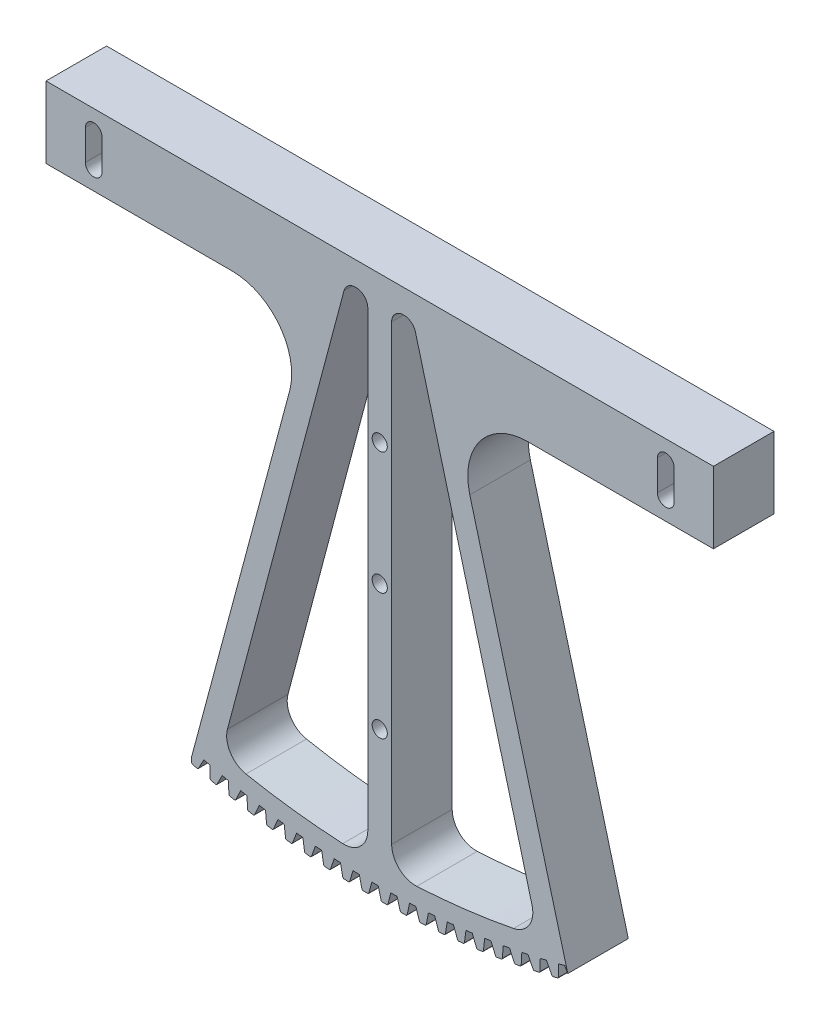
SolidWorks part; units mm, degrees
ref_plane "Front Plane" through (0, 0, 0) normal (0, 0, 1) x (1, 0, 0)
ref_plane "Top Plane" through (0, 0, 0) normal (0, 1, 0) x (1, 0, 0)
ref_plane "Right Plane" through (0, 0, 0) normal (1, 0, 0) x (0, 0, -1)
sketch "Sketch3" plane through (0, 0, 0) normal (0, 0, 1) x (1, 0, 0)
  line L0 (0, 0) -> (0, -304.8) construction
  line L1 (-21.234, -79.2464) -> (-78.888, -294.4142)
  line L2 (21.234, -79.2464) -> (78.888, -294.4142)
  line L4 (-140, -79.56) -> (140, -79.56)
  line L5 (-140, -79.56) -> (-140, -109.56)
  line L6 (-140, -109.56) -> (140, -109.56)
  line L7 (140, -79.56) -> (140, -109.56)
  line L8 (0, -109.56) -> (0, -79.56) construction
  line L9 (-140, -94.56) -> (140, -94.56) construction
  arc A0 (-78.888, -294.4142) -> (78.888, -294.4142) centre (0, 0) ccw
  point P269 (0, -94.56)
  dimension "D1" = 304.8
  dimension "D4" = 79.56
  dimension "D5" = 30
  dimension "D6" = 280
  dimension "D7" = 140
extrude "Boss-Extrude2" add sketch "Sketch3" along normal blind 25.4 contours L7 L4 L2 L6 | L1 L6 L2 L4 | L1 L4 L2 | L5 L6 L1 L4 | L1 A0 L2 L6 region at (0, -95.3531, 0) region at (-82.6452, -94.3847, 0) region at (0, -220.3694, 0) region at (82.6452, -94.3847, 0)
fillet "Fillet1" radius 25 2 edges at (-29.3565, -109.56, 12.7) (29.3565, -109.56, 12.7)
sketch "Sketch4" plane through (0, -79.56, 0) normal (0, 1, 0) x (1, 0, 0)
  line L1 (-140, 0) -> (140, 0)
  line L2 (-140, 0) -> (-140, -25.4)
  line L3 (-140, -25.4) -> (140, -25.4)
  line L4 (140, 0) -> (140, -25.4)
  line L5 (0, -25.4) -> (0, 0) construction
  line L6 (-140, -12.7) -> (140, -12.7) construction
  point P252 (0, -12.7)
sketch "Sketch5" plane through (0, 0, 0) normal (0, 0, -1) x (-1, 0, 0)
  line L0 (-123.5, -94.56) -> (-123.5, -100.91)
  line L1 (-116.5, -94.56) -> (-116.5, -100.91)
  line L2 (116.5, -94.56) -> (116.5, -88.21)
  line L3 (140, -79.56) -> (-140, -79.56) construction
  line L4 (-120, -88.21) -> (-120, -100.91) construction
  line L5 (0, -79.56) -> (0, -109.56) construction
  line L6 (-116.5, -94.56) -> (-116.5, -88.21)
  line L7 (-123.5, -94.56) -> (-123.5, -88.21)
  line L8 (116.5, -94.56) -> (116.5, -100.91)
  line L9 (123.5, -94.56) -> (123.5, -100.91)
  line L10 (123.5, -94.56) -> (123.5, -88.21)
  line L11 (-140, -79.56) -> (-140, -109.56) construction
  line L12 (120, -88.21) -> (120, -100.91) construction
  arc A1 (-116.5, -88.21) -> (-123.5, -88.21) centre (-120, -88.21) ccw
  arc A2 (-123.5, -100.91) -> (-116.5, -100.91) centre (-120, -100.91) ccw
  arc A3 (123.5, -100.91) -> (116.5, -100.91) centre (120, -100.91) cw
  arc A4 (116.5, -88.21) -> (123.5, -88.21) centre (120, -88.21) cw
  dimension "D1" = 16.5
  dimension "D2" = 7
  dimension "D3" = 8.65
  dimension "D5" = 3.5
  dimension "D4" = 6.35
sketch "Sketch13" plane through (0, 0, 0) normal (0, 0, -1) x (-1, 0, 0)
  line L0 (0, 0) -> (78.888, -294.4142)
  line L1 (0, 0) -> (-78.888, -294.4142)
  arc A0 (-78.888, -294.4142) -> (78.888, -294.4142) centre (0, 0) ccw
  arc A1 (-78.888, -294.4142) -> (78.888, -294.4142) centre (0, 0) ccw construction
  arc A2 (-78.888, -294.4142) -> (78.888, -294.4142) centre (0, 0) ccw
  circle A3 centre (0, 0) radius 304.8
  dimension "D1" = 609.6
sketch "Sketch14" plane through (0, 0, 0) normal (0, 0, -1) x (-1, 0, 0)
  line L0 (0, 0) -> (80.0203, -298.6399) construction
  line L2 (78.888, -294.4142) -> (78.9109, -297.0369)
  line L3 (78.9109, -297.0369) -> (76.2891, -297.7211)
  line L18 (76.2891, -297.7211) -> (75.0275, -295.4216)
  line L20 (0, 0) -> (-79.2746, -295.8555) construction
  line L32 (78.888, -294.4142) -> (75.0275, -295.4216)
  line L33 (75.0275, -295.4216) -> (78.888, -294.4142)
  line L34 (0, 0) -> (-75.3952, -296.8678) construction
  line L35 (0, 0) -> (-71.5028, -297.8293) construction
  line L36 (0, 0) -> (-67.5982, -298.7397) construction
  line L37 (0, 0) -> (-63.6821, -299.5989) construction
  line L38 (0, 0) -> (-59.755, -300.4068) construction
  line L39 (0, 0) -> (-55.8176, -301.1633) construction
  line L40 (0, 0) -> (-51.8707, -301.8681) construction
  line L41 (0, 0) -> (-47.9149, -302.5212) construction
  line L42 (0, 0) -> (-43.951, -303.1225) construction
  line L43 (0, 0) -> (-39.9794, -303.6718) construction
  line L44 (0, 0) -> (-36.0011, -304.1691) construction
  line L45 (0, 0) -> (-32.0165, -304.6143) construction
  line L46 (0, 0) -> (-28.0265, -305.0073) construction
  line L47 (0, 0) -> (-24.0316, -305.348) construction
  line L48 (0, 0) -> (-20.0327, -305.6364) construction
  line L49 (0, 0) -> (-16.0303, -305.8724) construction
  line L50 (0, 0) -> (-12.0252, -306.0561) construction
  line L51 (0, 0) -> (-8.018, -306.1873) construction
  line L52 (0, 0) -> (-4.0094, -306.266) construction
  line L53 (0, 0) -> (-0.0002, -306.2922) construction
  line L54 (0, 0) -> (4.0091, -306.266) construction
  line L55 (0, 0) -> (8.0176, -306.1873) construction
  line L56 (0, 0) -> (12.0248, -306.0561) construction
  line L57 (0, 0) -> (16.03, -305.8725) construction
  line L58 (0, 0) -> (20.0323, -305.6364) construction
  line L59 (0, 0) -> (24.0313, -305.348) construction
  line L60 (0, 0) -> (28.0261, -305.0073) construction
  line L61 (0, 0) -> (32.0162, -304.6143) construction
  line L62 (0, 0) -> (36.0007, -304.1691) construction
  line L63 (0, 0) -> (39.9791, -303.6719) construction
  line L64 (0, 0) -> (43.9506, -303.1225) construction
  line L65 (0, 0) -> (47.9146, -302.5213) construction
  line L66 (0, 0) -> (51.8704, -301.8682) construction
  line L67 (0, 0) -> (55.8173, -301.1633) construction
  line L68 (0, 0) -> (59.7546, -300.4069) construction
  line L69 (0, 0) -> (63.6817, -299.599) construction
  line L70 (0, 0) -> (67.5979, -298.7398) construction
  line L71 (0, 0) -> (71.5025, -297.8293) construction
  line L72 (0, 0) -> (75.3948, -296.8679) construction
  line L73 (0, 0) -> (-79.2746, -295.8555) construction
  line L74 (0, 0) -> (-75.3952, -296.8678) construction
  line L137 (37.789, -141.0305) -> (78.888, -294.4142) construction
  line L138 (-140, -79.56) -> (-140, -109.56)
  line L139 (-140, -109.56) -> (-61.9371, -109.56)
  line L140 (-37.789, -141.0305) -> (-78.888, -294.4142)
  line L141 (78.888, -294.4142) -> (37.789, -141.0305)
  line L142 (61.9371, -109.56) -> (140, -109.56)
  line L143 (140, -109.56) -> (140, -79.56)
  line L144 (140, -79.56) -> (-140, -79.56)
  line L145 (-140, -79.56) -> (-140, -109.56)
  line L146 (-140, -109.56) -> (-61.9371, -109.56)
  line L147 (-37.789, -141.0305) -> (-78.888, -294.4142)
  line L149 (61.9371, -109.56) -> (140, -109.56)
  line L150 (140, -109.56) -> (140, -79.56)
  line L151 (140, -79.56) -> (-140, -79.56)
  circle A0 centre (0, 0) radius 307.34
  circle A1 centre (0, 0) radius 302.26
  arc A3 (-37.789, -141.0305) -> (-61.9371, -109.56) centre (-61.9371, -134.56) ccw
  arc A5 (61.9371, -109.56) -> (37.789, -141.0305) centre (61.9371, -134.56) ccw
  arc A6 (-37.789, -141.0305) -> (-61.9371, -109.56) centre (-61.9371, -134.56) ccw
  arc A8 (61.9371, -109.56) -> (37.789, -141.0305) centre (61.9371, -134.56) ccw
  arc A11 (-78.888, -294.4142) -> (78.888, -294.4142) centre (0, 0) ccw
  arc A12 (-78.888, -294.4142) -> (78.888, -294.4142) centre (0, 0) ccw
  arc M181 (-78.888, -294.4142) -> (78.888, -294.4142) centre (0, 0) ccw
  dimension "D5" = 614.68
  dimension "D6" = 30
  dimension "D7" = 40
  dimension "D4" = 604.52
  dimension "D1" = 14.5
  dimension "D3" = 14.5
  dimension "D8" = 0.75
  dimension "D9" = 306.2922
  dimension "D10" = 0.75
  dimension "D2" = 0
extrude "Boss-Extrude4" add sketch "Sketch14" against normal up to surface (25.4 mm away) contours L2 M181 region at (-77.2591, -296.0724, 0) up to face at (0, -146.6727, 25.4)
sketch "Sketch15" plane through (0, 0, 0) normal (1, 0, 0) x (0, 0, -1)
  line L0 (0, 0) -> (-23.3364, 0) construction
sketch "Sketch16" plane through (0, 0, 0) normal (0, 0, -1) x (-1, 0, 0)
  line L0 (75.0275, -295.4216) -> (73.7653, -293.1208)
  line L1 (73.7653, -293.1208) -> (71.1999, -293.7544)
  line L2 (71.1999, -293.7544) -> (71.1541, -296.3784)
  line L3 (0, 0) -> (71.5025, -297.8293) construction
  line L4 (0, 0) -> (75.3948, -296.8679) construction
  circle A0 centre (0, 0) radius 302.26 construction
  arc A1 (-78.888, -294.4142) -> (78.888, -294.4142) centre (0, 0) ccw construction
  dimension "D1" = 14.5
  dimension "D2" = 14.5
extrude "Cut-Extrude2" cut sketch "Sketch16" against normal through all and the other way through all
fillet "Fillet4" radius 0.5 2 edges at (-76.2891, -297.7211, 12.7) (-78.9109, -297.0369, 12.7)
pattern_circular "CirPattern8" count 20 every 1.5 about axis through (0, 0, 0) along (0, 0, 1) of "Cut-Extrude2", "Boss-Extrude4", "Fillet4"
extrude "Cut-Extrude3" cut sketch "Sketch5" against normal through all
sketch "Sketch17" plane through (0, 0, 25.4) normal (0, 0, 1) x (1, 0, 0)
  line L0 (0, -89.56) -> (0, -140.87) construction
  line L1 (-4.9975, -89.56) -> (-13.9975, -89.56) construction
  line L2 (5, -89.56) -> (13.9975, -89.56) construction
  line L3 (0, 0) -> (78.888, -294.4142) construction
  line L4 (13.9975, -89.56) -> (5, -89.56) construction
  line L5 (0, 0) -> (-78.888, -294.4142) construction
  line L6 (5, -192.18) -> (41.3123, -192.18) construction
  line L7 (-13.9975, -89.56) -> (-11.3363, -79.56) construction
  line L8 (-13.9975, -89.56) -> (-69.1613, -296.8497) construction
  line L9 (-74.9529, -279.7282) -> (-65.2893, -282.2998) construction
  line L10 (-4.9975, -192.1745) -> (-41.3052, -192.1745) construction
  line L11 (13.9975, -89.56) -> (69.1728, -296.8504) construction
  line L12 (64.3749, -278.8253) -> (73.8713, -275.6914) construction
  line L13 (-140, -79.56) -> (140, -79.56) construction
  line L14 (-69.1613, -296.8497) -> (-66.5896, -287.1862) construction
  line L15 (69.1728, -296.8504) -> (66.5993, -287.1821) construction
  line L16 (-13.9975, -89.56) -> (-23.9975, -89.56) construction
  line L17 (5, -89.56) -> (5, -294.7576) construction
  line L18 (-21.318, -79.56) -> (21.318, -79.56) construction
  line L19 (-4.9975, -89.56) -> (-4.9975, -294.7577) construction
  line L20 (-4.9975, -89.56) -> (-13.9975, -89.56)
  line L21 (-13.9975, -89.56) -> (-66.5896, -287.1862)
  line L22 (-4.9975, -89.56) -> (-4.9975, -294.7577)
  line L23 (5, -89.56) -> (13.9975, -89.56)
  line L24 (13.9975, -89.56) -> (66.5993, -287.1821)
  line L25 (5, -294.7576) -> (5, -89.56)
  line L26 (21.318, -79.56) -> (76.5399, -285.6507) construction
  line L27 (76.5399, -285.6507) -> (66.8763, -288.2228) construction
  line L28 (13.9975, -89.56) -> (23.9975, -89.56) construction
  line L29 (0, -140.87) -> (0, -192.18) construction
  line L30 (0, -192.18) -> (0, -245.0775) construction
  line L31 (0, -245.0775) -> (0, -304.8) construction
  arc A0 (-78.888, -294.4142) -> (78.888, -294.4142) centre (0, 0) ccw construction
  arc A1 (-66.5896, -287.1862) -> (-4.9975, -294.7577) centre (-0.004, 0.166) ccw
  arc A2 (5, -294.7576) -> (66.5993, -287.1821) centre (-0.004, 0.166) ccw
  circle A3 centre (0, -140.87) radius 3.175
  circle A4 centre (0, -192.18) radius 3.175
  circle A5 centre (0, -245.0775) radius 3.175
  dimension "D3" = 0.166
  dimension "D4" = 52.8975
  dimension "D11" = 10
  dimension "D14" = 6.35
  dimension "D1" = 10
  dimension "D2" = 10.0001
  dimension "D5" = 205.1976
  dimension "D6" = 0.095
  dimension "D7" = 9
  dimension "D8" = 197.6262
  dimension "D9" = 10
  dimension "D10" = 10
  dimension "D12" = 10
  dimension "D13" = 0.098
  dimension "D15" = 51.31
  dimension "D16" = 51.31
extrude "Cut-Extrude5" cut sketch "Sketch17" against normal through all
fillet "Fillet6" radius 10 4 edges at (-4.9975, -294.7577, 12.7) (-66.5896, -287.1862, 12.7) (5, -294.7576, 12.7) (66.5993, -287.1821, 12.7)
fillet "Fillet7" radius 5 4 edges at (-4.9975, -89.56, 12.7) (13.9975, -89.56, 12.7) (5, -89.56, 12.7) (-13.9975, -89.56, 12.7)
equation "\"D7@Sketch3\"=\"D6@Sketch3\"/2"
